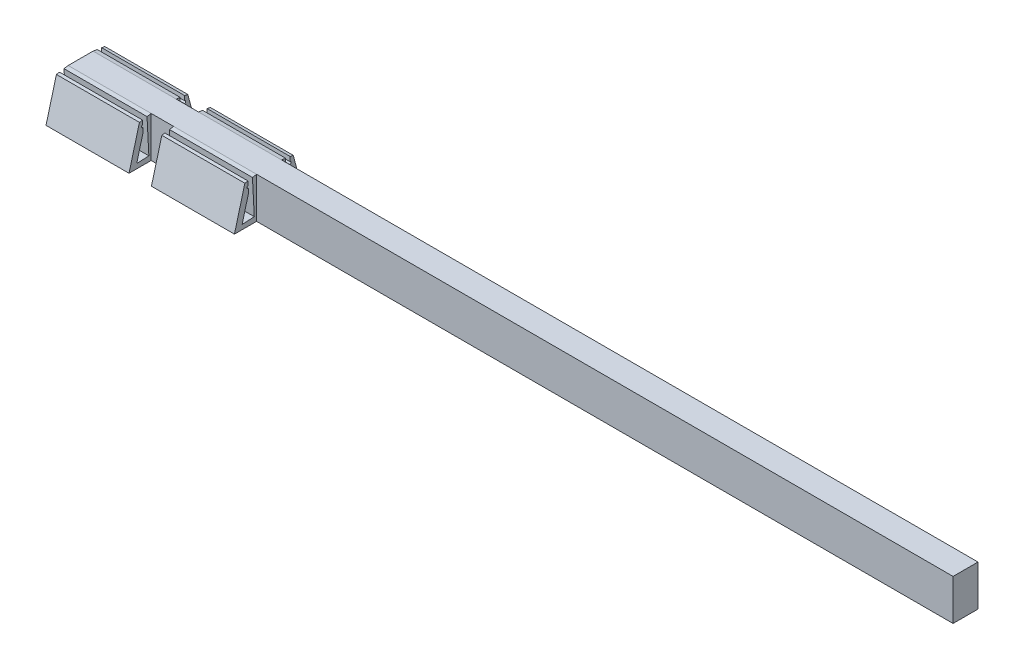
SolidWorks part; units mm, degrees
ref_plane "Front Plane" through (0, 0, 0) normal (0, 0, 1) x (1, 0, 0)
ref_plane "Top Plane" through (0, 0, 0) normal (0, 1, 0) x (1, 0, 0)
ref_plane "Right Plane" through (0, 0, 0) normal (1, 0, 0) x (0, 0, -1)
sketch "Sketch1" plane through (0, 0, 0) normal (1, 0, 0) x (0, 0, -1)
  line L0 (3.6311, 0.3059) -> (9.4677, 0) construction
  line L1 (3.904, 5.5131) -> (4.9077, 5.4605) construction
  line L2 (6.2203, 9.4885) -> (6.0816, 6.8415) construction
  line L3 (6.0816, 6.8415) -> (7.6191, 1.1033)
  line L4 (7.6191, 1.1033) -> (4.6874, 1.2569)
  line L5 (4.6874, 1.2569) -> (5.128, 9.664)
  line L6 (5.128, 9.664) -> (4.13, 9.8243)
  line L7 (4.13, 9.8243) -> (3.6311, 0.3059) construction
  line L8 (6.2203, 9.4885) -> (6.1666, 8.4646)
  line L9 (6.1352, 7.8654) -> (6.0816, 6.8415)
  line L10 (6.2203, 9.4885) -> (6.9569, 9.3702)
  line L11 (6.9569, 9.3702) -> (9.4677, 0)
  line L12 (6.1532, 1.1801) -> (6.1006, 0.1765) construction
  line L13 (1.128, 0) -> (1.128, 7.6812) construction
  line L14 (-3.8973, 1.1801) -> (-3.8447, 0.1765) construction
  line L15 (-5.3632, 1.1033) -> (-2.4314, 1.2569)
  line L16 (-3.9644, 9.4885) -> (-3.8256, 6.8415) construction
  line L17 (-1.6481, 5.5131) -> (-2.6517, 5.4605) construction
  line L18 (-1.3752, 0.3059) -> (-7.2117, 0) construction
  line L19 (-4.701, 9.3702) -> (-7.2117, 0)
  line L20 (-3.9644, 9.4885) -> (-4.701, 9.3702)
  line L21 (-3.8793, 7.8654) -> (-3.8256, 6.8415)
  line L22 (-3.9644, 9.4885) -> (-3.9107, 8.4646)
  line L23 (-1.874, 9.8243) -> (-1.3752, 0.3059) construction
  line L24 (-2.872, 9.664) -> (-1.874, 9.8243)
  line L25 (-2.4314, 1.2569) -> (-2.872, 9.664)
  line L26 (-3.8256, 6.8415) -> (-5.3632, 1.1033)
  line L27 (-1.874, 9.8243) -> (4.13, 9.8243)
  line L28 (-7.2117, 0) -> (-2.3656, 0)
  line L29 (-2.4314, 1.2569) -> (-2.3656, 0)
  line L30 (4.6874, 1.2569) -> (4.6215, 0)
  line L31 (-2.3656, 0) -> (4.6215, 0)
  line L32 (4.6215, 0) -> (9.4677, 0)
  arc A0 (6.1666, 8.4646) -> (6.1352, 7.8654) centre (6.1509, 8.165) cw
  arc A1 (-3.9107, 8.4646) -> (-3.8793, 7.8654) centre (-3.895, 8.165) ccw
  dimension "D1" = 0.3
  dimension "D2" = 1.1
  dimension "D3" = 72
  dimension "D4" = 1.5
  dimension "D5" = 8
extrude "Clip #1" add sketch "Sketch1" along normal mid plane 20 contours L28 L19 L20 L22 A1 L21 L26 L15 L25 L24 L27 L6 L5 L4 L3 L9 A0 L8 L10 L11 L32 L31
sketch "Sketch4" plane through (0, 0, 0) normal (1, 0, 0) x (0, 0, -1)
  line L0 (-1.874, 9.8243) -> (-1.874, 0)
  line L1 (-2.3656, 0) -> (4.6215, 0) construction
  line L2 (-1.874, 9.8243) -> (4.13, 9.8243)
  line L3 (4.13, 9.8243) -> (4.13, 0)
  line L4 (4.13, 0) -> (-1.874, 0)
extrude "Center beam" add sketch "Sketch4" along normal blind 203.2
sketch "Sketch5" plane through (0, 0, 0) normal (0, 1, 0) x (1, 0, 0)
  line L0 (76.2, -58.3264) -> (76.2, 110.1277) construction
  line L1 (25.4, 19.5305) -> (25.4, 187.9846) construction
  line L2 (127, 16.9825) -> (127, 185.4366) construction
  line L3 (177.8, 22.3617) -> (177.8, 190.8158) construction
  dimension "D1" = 25.4
  dimension "D2" = 50.8
  dimension "D3" = 50.8
  dimension "D4" = 50.8
sketch3d "3DSketch2" plane through (0, 0, 0) normal (0, 0, 1) x (1, 0, 0)
  dimension "D1" = 25.4
sketch "Sketch6" plane through (25.4, 0, 0) normal (1, 0, 0) x (0, 0, -1)
  line L0 (7.6191, 1.1033) -> (4.6874, 1.2569) construction
  line L5 (6.0816, 6.8415) -> (7.6191, 1.1033) construction
  line L6 (6.1352, 7.8654) -> (6.0816, 6.8415) construction
  line L7 (6.2203, 9.4885) -> (6.1666, 8.4646) construction
  line L8 (6.2203, 9.4885) -> (6.9569, 9.3702) construction
  line L9 (6.9569, 9.3702) -> (9.4677, 0) construction
  line L10 (4.6215, 0) -> (9.4677, 0) construction
  line L11 (4.6874, 1.2569) -> (5.128, 9.664) construction
  line L12 (5.128, 9.664) -> (4.13, 9.8243) construction
  line L13 (-1.874, 9.8243) -> (4.13, 9.8243) construction
  line L14 (-2.872, 9.664) -> (-1.874, 9.8243) construction
  line L15 (-2.4314, 1.2569) -> (-2.872, 9.664) construction
  line L16 (4.6874, 1.2569) -> (4.6215, 0) construction
  line L17 (-7.2117, 0) -> (-2.3656, 0) construction
  line L18 (-4.701, 9.3702) -> (-7.2117, 0) construction
  line L19 (-3.9644, 9.4885) -> (-4.701, 9.3702) construction
  line L20 (-3.9644, 9.4885) -> (-3.9107, 8.4646) construction
  line L21 (-3.8793, 7.8654) -> (-3.8256, 6.8415) construction
  line L22 (-3.8256, 6.8415) -> (-5.3632, 1.1033) construction
  line L23 (-5.3632, 1.1033) -> (-2.4314, 1.2569) construction
  line L24 (-2.4314, 1.2569) -> (-2.3656, 0) construction
  line L25 (-2.3656, 0) -> (4.6215, 0) construction
  line L26 (7.6191, 1.1033) -> (4.6874, 1.2569)
  line L27 (6.0816, 6.8415) -> (7.6191, 1.1033)
  line L28 (6.1352, 7.8654) -> (6.0816, 6.8415)
  line L29 (6.2203, 9.4885) -> (6.1666, 8.4646)
  line L30 (6.2203, 9.4885) -> (6.9569, 9.3702)
  line L31 (6.9569, 9.3702) -> (9.4677, 0)
  line L32 (4.6215, 0) -> (9.4677, 0)
  line L33 (4.6874, 1.2569) -> (5.128, 9.664)
  line L34 (5.128, 9.664) -> (4.13, 9.8243)
  line L35 (-1.874, 9.8243) -> (4.13, 9.8243)
  line L36 (-2.872, 9.664) -> (-1.874, 9.8243)
  line L37 (-2.4314, 1.2569) -> (-2.872, 9.664)
  line L38 (4.6874, 1.2569) -> (4.6215, 0) construction
  line L39 (-7.2117, 0) -> (-2.3656, 0)
  line L40 (-4.701, 9.3702) -> (-7.2117, 0)
  line L41 (-3.9644, 9.4885) -> (-4.701, 9.3702)
  line L42 (-3.9644, 9.4885) -> (-3.9107, 8.4646)
  line L43 (-3.8793, 7.8654) -> (-3.8256, 6.8415)
  line L44 (-3.8256, 6.8415) -> (-5.3632, 1.1033)
  line L45 (-5.3632, 1.1033) -> (-2.4314, 1.2569)
  line L46 (-2.4314, 1.2569) -> (-2.3656, 0) construction
  line L47 (-2.3656, 0) -> (4.6215, 0)
  arc A0 (6.1352, 7.8654) -> (6.1666, 8.4646) centre (6.1509, 8.165) ccw construction
  arc A1 (-3.9107, 8.4646) -> (-3.8793, 7.8654) centre (-3.895, 8.165) ccw construction
  arc A2 (6.1352, 7.8654) -> (6.1666, 8.4646) centre (6.1509, 8.165) ccw
  arc A3 (-3.9107, 8.4646) -> (-3.8793, 7.8654) centre (-3.895, 8.165) ccw
extrude "Boss-Extrude9" add sketch "Sketch6" along normal mid plane 20 contours L37 L36 L35 L34 L33 L26 L27 L28 A2 L29 L30 L31 L32 L47 L39 L40 L41 L42 A3 L43 L44 L45
